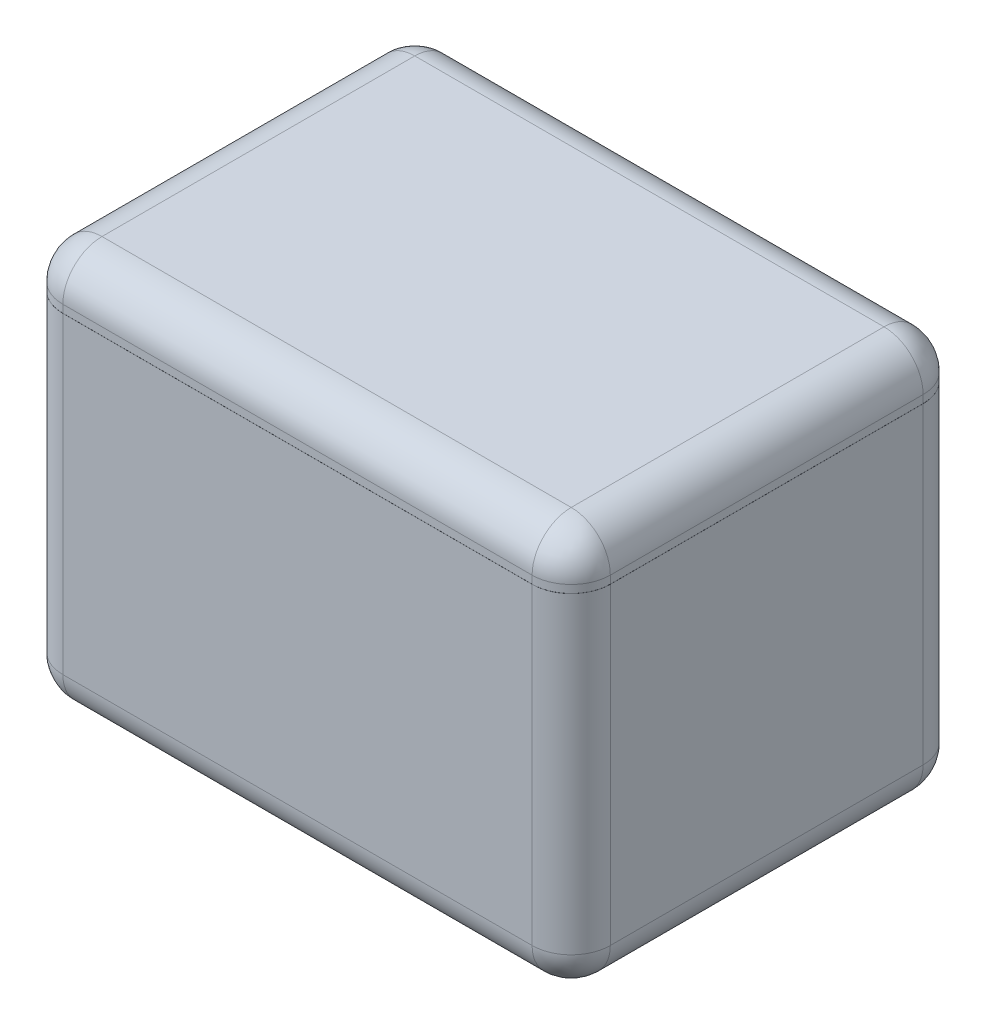
SolidWorks part; units mm, degrees
material "ABS"
ref_plane "Front Plane" through (0, 0, 0) normal (0, 0, 1) x (1, 0, 0)
ref_plane "Top Plane" through (0, 0, 0) normal (0, 1, 0) x (1, 0, 0)
ref_plane "Right Plane" through (0, 0, 0) normal (1, 0, 0) x (0, 0, -1)
sketch "Sketch1" plane through (0, 0, 0) normal (0, 1, 0) x (1, 0, 0)
  line L0 (-32, -22) -> (-32, 22)
  line L1 (35, -25) -> (-35, -25)
  line L2 (35, -25) -> (35, 25)
  line L3 (35, 25) -> (-35, 25)
  line L4 (-35, -25) -> (-35, 25)
  line L5 (35, -25) -> (-35, 25) construction
  line L6 (35, 25) -> (-35, -25) construction
  line L7 (32, 22) -> (-32, 22)
  line L8 (32, -22) -> (32, 22)
  line L9 (32, -22) -> (-32, -22)
  point P0 (0, 0)
  dimension "D1" = 50
  dimension "D2" = 70
  dimension "D3" = 3
extrude "Boss-Extrude1" add sketch "Sketch1" along normal blind 40
extrude "Boss-Extrude2" add sketch "Sketch1<2>" against normal blind 5 contours L4 L1 L2 L3 L8 L9 L0 L7 | L9 L8 L7 L0 region at (0, 0, 0) region at (0, 0, 24.1398)
sketch "Sketch1<2>" plane through (0, 0, 0) normal (0, 1, 0) x (1, 0, 0) same geometry as "Sketch1"
fillet "Fillet1" radius 5 4 edges at (0, -5, 25) (35, -5, 0) (0, -5, -25) (-35, -5, 0)
fillet "Fillet2" radius 5 4 edges at (32, 20, 22) (-32, 20, -22) (-32, 20, 22) (32, 20, -22)
fillet "Fillet3" radius 5 8 edges at (33.5355, -3.5355, 23.5355) (-33.5355, -3.5355, 23.5355) (33.5355, -3.5355, -23.5355) (-33.5355, -3.5355, -23.5355) (35, 20, 25) (-35, 20, 25) (35, 20, -25) (-35, 20, -25)
sketch "Sketch2" plane through (0, 40, 0) normal (0, 1, 0) x (1, 0, 0)
  line L1 (26.75, -21.75) -> (-26.75, -21.75)
  line L2 (31.75, -16.75) -> (31.75, 16.75)
  line L3 (26.75, 21.75) -> (-26.75, 21.75)
  line L4 (-31.75, -16.75) -> (-31.75, 16.75)
  line L5 (31.75, -21.75) -> (-31.75, 21.75) construction
  line L6 (31.75, 21.75) -> (-31.75, -21.75) construction
  arc A0 (-26.75, -21.75) -> (-31.75, -16.75) centre (-26.75, -16.75) cw
  arc A1 (26.75, -21.75) -> (31.75, -16.75) centre (26.75, -16.75) ccw
  arc A2 (31.75, 16.75) -> (26.75, 21.75) centre (26.75, 16.75) ccw
  arc A3 (-26.75, 21.75) -> (-31.75, 16.75) centre (-26.75, 16.75) ccw
  point P0 (0, 0)
  dimension "D3" = 5
  dimension "D1" = 43.5
  dimension "D2" = 63.5
extrude "Boss-Extrude3" add sketch "Sketch2" against normal blind 5 and the other way blind 0.01 separate body
sketch "Sketch3" plane through (0, 40.01, 0) normal (0, 1, 0) x (1, 0, 0)
  line L0 (-30, -25) -> (30, -25) construction
  line L1 (30, 25) -> (-30, 25)
  line L2 (35, 20) -> (35, -20)
  line L3 (30, -25) -> (-30, -25)
  line L4 (-35, 20) -> (-35, -20)
  line L5 (35, 25) -> (-35, -25) construction
  line L6 (35, -25) -> (-35, 25) construction
  line L7 (-35, 20) -> (-35, -20) construction
  arc A0 (30, 25) -> (35, 20) centre (30, 20) cw
  arc A1 (35, -20) -> (30, -25) centre (30, -20) cw
  arc A2 (-30, -25) -> (-35, -20) centre (-30, -20) cw
  arc A3 (-30, 25) -> (-35, 20) centre (-30, 20) ccw
  point P0 (0, 0)
  dimension "D1" = 5
extrude "Boss-Extrude4" add sketch "Sketch3" along normal blind 6
fillet "Fillet4" radius 5 8 edges at (35, 46.01, 0) (33.5355, 46.01, 23.5355) (0, 46.01, 25) (-33.5355, 46.01, 23.5355) (-35, 46.01, 0) (-33.5355, 46.01, -23.5355) (0, 46.01, -25) (33.5355, 46.01, -23.5355)
sketch "Sketch4" plane through (0, 0, -25) normal (0, 0, -1) x (-1, 0, 0)
  line L0 (-30, 10) -> (30, 10) construction
  line L1 (-30, 40) -> (-30, 0) construction
  line L2 (30, 0) -> (30, 40) construction
  text T0 "IGNITION BOX" font "Comic Sans MS" height in points 20
  dimension "D1" = 10
extrude "Cut-Extrude1" cut sketch "Sketch4" against normal blind 1
sketch "Sketch5" plane through (-35, 0, 0) normal (-1, 0, 0) x (0, 0, 1)
  line L1 (7.5562, 13.4937) -> (-7.5562, 13.4937)
  line L2 (7.5562, 13.4937) -> (7.5562, 17.4171)
  line L3 (7.5562, 17.4171) -> (-7.5562, 17.4171)
  line L4 (-7.5562, 13.4937) -> (-7.5562, 17.4171)
  line L5 (7.5562, 13.4937) -> (-7.5562, 17.4171) construction
  line L6 (7.5562, 17.4171) -> (-7.5562, 13.4937) construction
  point P0 (0, 15.4554)
extrude "Cut-Extrude2" cut sketch "Sketch5" against normal up to next (3 mm away)
